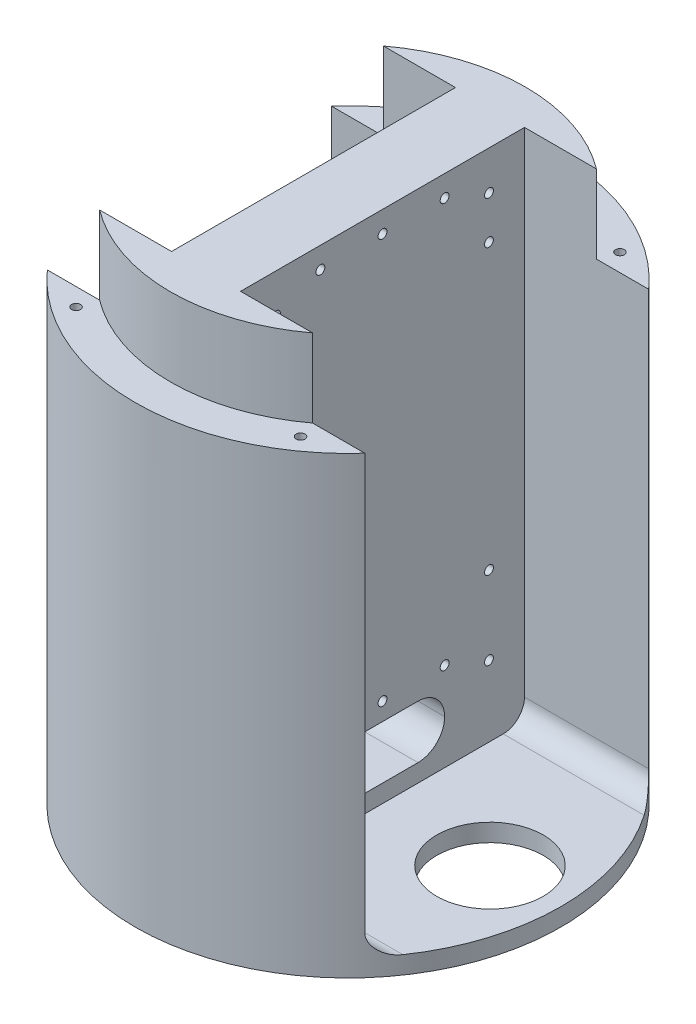
SolidWorks part; units mm, degrees
material "5052-O"
ref_plane "正面" through (0, 0, 0) normal (0, 0, 1) x (1, 0, 0)
ref_plane "平面" through (0, 0, 0) normal (0, 1, 0) x (1, 0, 0)
ref_plane "右側面" through (0, 0, 0) normal (1, 0, 0) x (0, 0, -1)
sketch "ｽｹｯﾁ1" plane through (0, 0, 0) normal (0, 1, 0) x (1, 0, 0)
  circle A0 centre (0, 0) radius 60
  dimension "D1" = 120
extrude "ﾎﾞｽ - 押し出し1" add sketch "ｽｹｯﾁ1" along normal blind 150
sketch "ｽｹｯﾁ2" plane through (0, 150, 0) normal (0, 1, 0) x (1, 0, 0)
  line L0 (-44.7214, 40) -> (-9.7214, 40)
  line L1 (-9.7214, 40) -> (-9.7214, -40)
  line L2 (-9.7214, -40) -> (-44.7214, -40)
  circle A0 centre (0, 0) radius 60 construction
  arc A1 (-44.7214, -40) -> (-44.7214, 40) centre (0, 0) cw
  dimension "D1" = 80
  dimension "D2" = 40
  dimension "D3" = 35
extrude "ｶｯﾄ - 押し出し1" cut sketch "ｽｹｯﾁ2" against normal blind 145
mirror "ﾐﾗｰ1" about plane through (0, 0, 0) normal (1, 0, 0) of "ｶｯﾄ - 押し出し1"
sketch "ｽｹｯﾁ3" plane through (0, 0, 0) normal (0, -1, 0) x (1, 0, 0)
  line L0 (0, 30) -> (0, 0) construction
  circle A0 centre (0, 30) radius 3
  dimension "D1" = 6
  dimension "D2" = 30
hole_wizard "M6x1.0(20mm) Base_Plateへの固定用ねじ穴" positions "3Dｽｹｯﾁ1" profile "ｽｹｯﾁ4" tap size "M6x1.0" standard "JIS"
sketch3d "3Dｽｹｯﾁ1"
  point P0 (0, 0, 30)
sketch "ｽｹｯﾁ4" plane through (0, 0, 30) normal (1, 0, 0) x (0, 0, -1)
  line L0 (0, 0) -> (0, 18.5022)
  line L1 (0, 18.5022) -> (2.5, 17)
  line L2 (2.5, 17) -> (2.5, 0)
  line L5 (2.5, 0) -> (0, 0)
  line L10 (0, 18.5022) -> (-2.5, 17) construction
  line L11 (0, -6.35) -> (0, 107.95) construction
  dimension "ねじ下穴ﾄﾞﾘﾙ直径" = 5
  dimension "ねじ下穴ﾄﾞﾘﾙの深さ" = 17
  dimension "ﾄﾞﾘﾙ角度" = 118
cosmetic thread "穴のねじ山21" parameters "D1"=12, "D2"=6
mirror "ﾐﾗｰ2" about plane through (0, 0, 0) normal (0, 0, 1) of "M6x1.0(20mm) Base_Plateへの固定用ねじ穴"
sketch "ｽｹｯﾁ8" plane through (9.7214, 0, 0) normal (1, 0, 0) x (0, 0, -1)
  line L0 (-40, 5) -> (40, 5) construction
  line L1 (0, 0) -> (0, 150) construction
  line L2 (-40, 150) -> (40, 150) construction
  circle A0 centre (0, 30) radius 1.5
  circle A1 centre (0, 144) radius 1.5
  circle A2 centre (17.5, 144) radius 1.5
  circle A3 centre (-17.5, 144) radius 1.5
  circle A4 centre (-17.5, 30) radius 1.5
  circle A5 centre (17.5, 30) radius 1.5
  dimension "D3" = 3
  dimension "D4" = 3
  dimension "D5" = 3
  dimension "D6" = 3
  dimension "D9" = 3
  dimension "D10" = 3
  dimension "D1" = 25
  dimension "D2" = 114
  dimension "D7" = 17.5
  dimension "D8" = 17.5
  dimension "D11" = 114
  dimension "D12" = 114
  dimension "D13" = 17.5
  dimension "D14" = 17.5
  dimension "D15" = 25
  dimension "D16" = 25
hole_wizard "M3x0.5(6mm) 送信機固定用ねじ穴" positions "3Dｽｹｯﾁ3" profile "ｽｹｯﾁ9" tap size "M3x0.5" standard "JIS" end condition through all
sketch3d "3Dｽｹｯﾁ3"
  point P0 (9.7214, 144, 17.5)
  point P3 (9.7214, 144, 0)
  point P6 (9.7214, 144, -17.5)
  point P9 (9.7214, 30, 0)
  point P12 (9.7214, 30, 17.5)
  point P15 (9.7214, 30, -17.5)
sketch "ｽｹｯﾁ9" plane through (9.7214, 144, 17.5) normal (0, 1, 0) x (0, 0, -1)
  line L0 (0, 0) -> (0, 69.7214)
  line L1 (0, 69.7214) -> (1.25, 69.7214)
  line L2 (1.25, 69.7214) -> (1.25, 0)
  line L5 (1.25, 0) -> (0, 0)
  line L11 (0, -6.35) -> (0, 107.95) construction
  dimension "次ｻｰﾌｪｽまでのねじ下穴ﾄﾞﾘﾙ直径" = 2.5
  dimension "次ｻｰﾌｪｽまでのねじ下穴ﾄﾞﾘﾙの深さ" = 69.7214
cosmetic thread "穴のねじ山7" parameters "D2"=3
cosmetic thread "穴のねじ山8" parameters "D2"=3
cosmetic thread "穴のねじ山9" parameters "D2"=3
cosmetic thread "穴のねじ山10" parameters "D2"=3
cosmetic thread "穴のねじ山11" parameters "D2"=3
cosmetic thread "穴のねじ山12" parameters "D2"=3
sketch "ｽｹｯﾁ10" plane through (0, 150, 0) normal (0, 1, 0) x (1, 0, 0)
  line L0 (-9.7214, 40) -> (-44.7214, 40) construction
  line L1 (9.7214, 40) -> (44.7214, 40) construction
  line L2 (-9.7214, 40) -> (-44.7214, 40) construction
  line L3 (-30, 40) -> (-44.7214, 40)
  line L4 (30, 40) -> (44.7214, 40)
  arc A0 (-30, 40) -> (30, 40) centre (0, 0) cw
  arc A1 (44.7214, 40) -> (-44.7214, 40) centre (0, 0) ccw construction
  arc A2 (44.7214, 40) -> (-44.7214, 40) centre (0, 0) ccw
  dimension "D1" = 50
extrude "ｶｯﾄ - 押し出し2" cut sketch "ｽｹｯﾁ10" against normal blind 22
mirror "ﾐﾗｰ3" about plane through (0, 0, 0) normal (0, 0, 1) of "ｶｯﾄ - 押し出し2"
sketch "ｽｹｯﾁ11" plane through (0, 128, 0) normal (0, 1, 0) x (1, 0, 0)
  line L0 (0, 60) -> (0, -59.1604) construction
  circle A0 centre (-31.6228, 45) radius 1.5
  arc A1 (44.7214, 40) -> (-44.7214, 40) centre (0, 0) ccw construction
  circle A2 centre (31.6228, 45) radius 1.5
  dimension "D1" = 3
  dimension "D2" = 55
  dimension "D3" = 45
hole_wizard "M3x0.5(Spacer) Hub_Board固定用ねじ穴" positions "3Dｽｹｯﾁ4" profile "ｽｹｯﾁ12" tap size "M3x0.5" standard "JIS"
sketch3d "3Dｽｹｯﾁ4"
  point P0 (-31.6228, 128, -45)
  point P3 (31.6228, 128, -45)
sketch "ｽｹｯﾁ12" plane through (-31.6228, 128, -45) normal (1, 0, 0) x (0, 0, 1)
  line L0 (0, 0) -> (0, 9.2511)
  line L1 (0, 9.2511) -> (1.25, 8.5)
  line L2 (1.25, 8.5) -> (1.25, 0)
  line L5 (1.25, 0) -> (0, 0)
  line L10 (0, 9.2511) -> (-1.25, 8.5) construction
  line L11 (0, -6.35) -> (0, 107.95) construction
  dimension "ねじ下穴ﾄﾞﾘﾙ直径" = 2.5
  dimension "ねじ下穴ﾄﾞﾘﾙの深さ" = 8.5
  dimension "ﾄﾞﾘﾙ角度" = 118
cosmetic thread "穴のねじ山5" parameters "D1"=6, "D2"=3
cosmetic thread "穴のねじ山6" parameters "D1"=6, "D2"=3
mirror "ﾐﾗｰ4" about plane through (0, 0, 0) normal (0, 0, 1) of "M3x0.5(Spacer) Hub_Board固定用ねじ穴"
sketch "ｽｹｯﾁ13" plane through (0, 5, 0) normal (0, 1, 0) x (1, 0, 0)
  line L0 (-25, 20) -> (-56.5685, 20)
  line L1 (-25, -20) -> (-56.5685, -20)
  line L2 (0, 0) -> (-60, 0) construction
  line L4 (-25, 20) -> (-25, -20)
  arc A1 (-44.7214, 40) -> (-44.7214, -40) centre (0, 0) ccw construction
  arc A2 (-56.5685, 20) -> (-56.5685, -20) centre (0, 0) ccw
  dimension "D1" = 40
  dimension "D2" = 20
  dimension "D4" = 25
extrude "アクセスポート" cut sketch "ｽｹｯﾁ13" against normal through all
sketch "ｽｹｯﾁ14" plane through (0, 0, 0) normal (0, -1, 0) x (1, 0, 0)
  line L0 (0, 0) -> (40, 0) construction
  circle A0 centre (40, 0) radius 15
  dimension "D1" = 30
  dimension "D2" = 40
extrude "キルスイッチ配線用穴" cut sketch "ｽｹｯﾁ14" against normal through all
sketch "ｽｹｯﾁ15" plane through (-9.7214, 0, 0) normal (-1, 0, 0) x (0, 0, 1)
  line L0 (-20, 5) -> (-40, 5) construction
  line L1 (40, 5) -> (40, 150) construction
  line L2 (-40, 128) -> (-40, 150) construction
  line L3 (-40, 5) -> (-40, 150) construction
  line L4 (40, 5) -> (-40, 5) construction
  line L5 (40, 128) -> (40, 150) construction
  circle A0 centre (30, 25) radius 1.5
  circle A1 centre (-30, 25) radius 1.5
  circle A2 centre (30, 139) radius 1.5
  circle A3 centre (-30, 139) radius 1.5
  dimension "D1" = 3
  dimension "D4" = 3
  dimension "D7" = 3
  dimension "D8" = 3
  dimension "D2" = 20
  dimension "D3" = 10
  dimension "D5" = 10
  dimension "D6" = 114
  dimension "D9" = 10
  dimension "D10" = 20
  dimension "D11" = 114
  dimension "D12" = 10
hole_wizard "M3x0.5(6mm) OBC固定用ねじ穴" positions "3Dｽｹｯﾁ5" profile "ｽｹｯﾁ16" tap size "M3x0.5" standard "JIS" end condition through all
sketch3d "3Dｽｹｯﾁ5"
  point P0 (-9.7214, 139, -30)
  point P3 (-9.7214, 139, 30)
  point P6 (-9.7214, 25, -30)
  point P9 (-9.7214, 25, 30)
sketch "ｽｹｯﾁ16" plane through (-9.7214, 139, -30) normal (0, 1, 0) x (0, 0, 1)
  line L0 (0, 0) -> (0, 69.7214)
  line L1 (0, 69.7214) -> (1.25, 69.7214)
  line L2 (1.25, 69.7214) -> (1.25, 0)
  line L5 (1.25, 0) -> (0, 0)
  line L11 (0, -6.35) -> (0, 107.95) construction
  dimension "次ｻｰﾌｪｽまでのねじ下穴ﾄﾞﾘﾙ直径" = 2.5
  dimension "次ｻｰﾌｪｽまでのねじ下穴ﾄﾞﾘﾙの深さ" = 69.7214
cosmetic thread "穴のねじ山13" parameters "D2"=3
cosmetic thread "穴のねじ山14" parameters "D2"=3
cosmetic thread "穴のねじ山15" parameters "D2"=3
cosmetic thread "穴のねじ山16" parameters "D2"=3
fillet "ﾌｨﾚｯﾄ1" radius 1 2 edges at (-25, 2.5, 20) (-25, 2.5, -20)
sketch "ｽｹｯﾁ17" plane through (0, 0, 0) normal (0, -1, 0) x (1, 0, 0)
  line L0 (0, 60) -> (0, -60) construction
  line L1 (-63.4415, 0) -> (65.9497, 0) construction
  circle A0 centre (-25, 46.7333) radius 2.5
  arc A1 (-56.5685, -20) -> (-56.5685, 20) centre (0, 0) ccw construction
  circle A2 centre (25, 46.7333) radius 2.5
  circle A3 centre (25, -46.7333) radius 2.5
  circle A4 centre (-25, -46.7333) radius 2.5
  dimension "D1" = 5
  dimension "D2" = 53
  dimension "D3" = 25
hole_wizard "M5x0.8(20mm) Basw_Plateへの固定用ねじ穴" positions "3Dｽｹｯﾁ6" profile "ｽｹｯﾁ18" tap size "M5x0.8" standard "JIS"
sketch3d "3Dｽｹｯﾁ6"
  point P0 (-25, 0, 46.7333)
  point P3 (25, 0, 46.7333)
  point P6 (-25, 0, -46.7333)
  point P9 (25, 0, -46.7333)
sketch "ｽｹｯﾁ18" plane through (-25, 0, 46.7333) normal (1, 0, 0) x (0, 0, -1)
  line L0 (0, 0) -> (0, 15.2618)
  line L1 (0, 15.2618) -> (2.1, 14)
  line L2 (2.1, 14) -> (2.1, 0)
  line L5 (2.1, 0) -> (0, 0)
  line L10 (0, 15.2618) -> (-2.1, 14) construction
  line L11 (0, -6.35) -> (0, 107.95) construction
  dimension "ねじ下穴ﾄﾞﾘﾙ直径" = 4.2
  dimension "ねじ下穴ﾄﾞﾘﾙの深さ" = 14
  dimension "ﾄﾞﾘﾙ角度" = 118
cosmetic thread "穴のねじ山17" parameters "D1"=10, "D2"=5
cosmetic thread "穴のねじ山18" parameters "D1"=10, "D2"=5
cosmetic thread "穴のねじ山19" parameters "D1"=10, "D2"=5
cosmetic thread "穴のねじ山20" parameters "D1"=10, "D2"=5
fillet "ﾌｨﾚｯﾄ2" radius 6 2 edges at (27.2214, 5, -40) (27.2214, 5, 40)
fillet "ﾌｨﾚｯﾄ3" radius 6 2 edges at (-27.2214, 5, -40) (-27.2214, 5, 40)
sketch "ｽｹｯﾁ19" plane through (9.7214, 0, 0) normal (1, 0, 0) x (0, 0, -1)
  line L1 (-17.5, 10) -> (17.5, 10)
  line L2 (-17.5, 10) -> (-17.5, 25)
  line L3 (-17.5, 25) -> (17.5, 25)
  line L4 (17.5, 10) -> (17.5, 25)
  line L5 (-17.5, 10) -> (17.5, 25) construction
  line L6 (-17.5, 25) -> (17.5, 10) construction
  line L7 (-40, 11) -> (-40, 150) construction
  line L8 (-34, 5) -> (34, 5) construction
  point P0 (0, 17.5)
  dimension "D1" = 35
  dimension "D2" = 15
  dimension "D3" = 5
  dimension "D4" = 40
extrude "ｶｯﾄ - 押し出し3" cut sketch "ｽｹｯﾁ19" against normal blind 48
fillet "ﾌｨﾚｯﾄ4" radius 7.5 4 edges at (0, 25, 17.5) (0, 10, 17.5) (0, 10, -17.5) (0, 25, -17.5)
hole_wizard "M3x0.5 ねじ穴1" [suppressed] positions "ｽｹｯﾁ22" profile "ｽｹｯﾁ21" tap size "M3x0.5" standard "JIS"
sketch "ｽｹｯﾁ22" plane through (0, 5, 0) normal (0, 1, 0) x (1, 0, 0)
  line L0 (-45, 27.5) -> (-30, -27.5) construction
  line L2 (-30, 27.5) -> (-45, -27.5) construction
  line L3 (-45, 27.5) -> (-30, 27.5) construction
  line L4 (-30, 27.5) -> (-30, -27.5) construction
  line L5 (-30, -27.5) -> (-45, -27.5) construction
  line L6 (-45, -27.5) -> (-45, 27.5) construction
  line L8 (0, 0) -> (-60, 0) construction
  point P0 (-45, 27.5)
  point P2 (-30, 27.5)
  point P4 (-30, -27.5)
  point P6 (-45, -27.5)
  point P44 (-30, 0)
  dimension "D1" = 55
  dimension "D2" = 30
  dimension "D3" = 15
sketch "ｽｹｯﾁ21" plane through (-45, 5, -27.5) normal (1, 0, 0) x (0, 0, 1)
  line L0 (0, 0) -> (0, 5)
  line L1 (0, 5) -> (1.25, 5)
  line L2 (1.25, 5) -> (1.25, 0)
  line L5 (1.25, 0) -> (0, 0)
  line L11 (0, -6.35) -> (0, 107.95) construction
  dimension "次ｻｰﾌｪｽまでのねじ下穴ﾄﾞﾘﾙ直径" = 2.5
  dimension "次ｻｰﾌｪｽまでのねじ下穴ﾄﾞﾘﾙの深さ" = 5
cosmetic thread "穴のねじ山1" [suppressed] parameters "D2"=3
cosmetic thread "穴のねじ山2" [suppressed] parameters "D2"=3
cosmetic thread "穴のねじ山3" [suppressed] parameters "D2"=3
cosmetic thread "穴のねじ山4" [suppressed] parameters "D2"=3
sketch "ｽｹｯﾁ23" plane through (0, 5, 0) normal (0, 1, 0) x (1, 0, 0)
  line L1 (-45, -25) -> (-25, -25) construction
  line L2 (-45, -25) -> (-45, 25) construction
  line L3 (-45, 25) -> (-25, 25) construction
  line L4 (-25, -25) -> (-25, 25) construction
  line L5 (-45, -25) -> (-25, 25) construction
  line L6 (-45, 25) -> (-25, -25) construction
  point P0 (-35, 0)
  dimension "D1" = 20
  dimension "D2" = 50
  dimension "D3" = 25
hole_wizard "M3x0.5 ねじ穴2" positions "3Dｽｹｯﾁ7" profile "ｽｹｯﾁ24" tap size "M3x0.5" standard "JIS" end condition through all
sketch3d "3Dｽｹｯﾁ7"
  point P0 (-45, 5, -25)
  point P3 (-25, 5, -25)
  point P6 (-25, 5, 25)
  point P9 (-45, 5, 25)
sketch "ｽｹｯﾁ24" plane through (-45, 5, -25) normal (1, 0, 0) x (0, 0, 1)
  line L0 (0, 0) -> (0, 5)
  line L1 (0, 5) -> (1.25, 5)
  line L2 (1.25, 5) -> (1.25, 0)
  line L5 (1.25, 0) -> (0, 0)
  line L11 (0, -6.35) -> (0, 107.95) construction
  dimension "ねじ山の主要直径" = 2.5
  dimension "次ｻｰﾌｪｽまでのねじ下穴ﾄﾞﾘﾙの深さ" = 5
cosmetic thread "ねじ山1" parameters "D2"=7.5
cosmetic thread "ねじ山2" parameters "D2"=7.5
cosmetic thread "ねじ山3" parameters "D2"=7.5
cosmetic thread "ねじ山4" parameters "D2"=7.5
sketch "ｽｹｯﾁ25" plane through (9.7214, 0, 0) normal (1, 0, 0) x (0, 0, -1)
  line L0 (0, 30) -> (0, 144) construction
  line L1 (30, 47) -> (-30, 47) construction
  line L2 (30, 47) -> (30, 127) construction
  line L3 (30, 127) -> (-30, 127) construction
  line L4 (-30, 47) -> (-30, 127) construction
  line L5 (30, 47) -> (-30, 127) construction
  line L6 (30, 127) -> (-30, 47) construction
  line L10 (-34, 5) -> (34, 5)
  line L11 (40, 11) -> (40, 150)
  line L12 (40, 150) -> (-40, 150)
  line L13 (-40, 150) -> (-40, 11)
  line L14 (-34, 5) -> (34, 5) construction
  line L15 (40, 11) -> (40, 150) construction
  line L16 (40, 150) -> (-40, 150) construction
  line L17 (-40, 150) -> (-40, 11) construction
  arc A2 (34, 5) -> (40, 11) centre (34, 11) ccw
  arc A3 (-40, 11) -> (-34, 5) centre (-34, 11) ccw
  arc A4 (34, 5) -> (40, 11) centre (34, 11) ccw construction
  arc A5 (-40, 11) -> (-34, 5) centre (-34, 11) ccw construction
  point P0 (0, 87)
  dimension "D1" = 60
  dimension "D2" = 80
  dimension "D3" = 0
hole_wizard "M3x0.5 ねじ穴3" positions "3Dｽｹｯﾁ8" profile "ｽｹｯﾁ26" tap size "M3x0.5" standard "JIS" end condition through all
sketch3d "3Dｽｹｯﾁ8"
  point P0 (9.7214, 127, 30)
  point P3 (9.7214, 47, 30)
  point P6 (9.7214, 47, -30)
  point P9 (9.7214, 127, -30)
sketch "ｽｹｯﾁ26" plane through (9.7214, 127, 30) normal (0, 1, 0) x (0, 0, -1)
  line L0 (0, 0) -> (0, 66.2899)
  line L1 (0, 66.2899) -> (1.25, 66.2899)
  line L2 (1.25, 66.2899) -> (1.25, 0)
  line L5 (1.25, 0) -> (0, 0)
  line L11 (0, -6.35) -> (0, 107.95) construction
  dimension "次ｻｰﾌｪｽまでのねじ下穴ﾄﾞﾘﾙ直径" = 2.5
  dimension "次ｻｰﾌｪｽまでのねじ下穴ﾄﾞﾘﾙの深さ" = 66.2899
cosmetic thread "穴のねじ山22" parameters "D2"=3
cosmetic thread "穴のねじ山23" parameters "D2"=3
cosmetic thread "穴のねじ山24" parameters "D2"=3
cosmetic thread "穴のねじ山25" parameters "D2"=3
